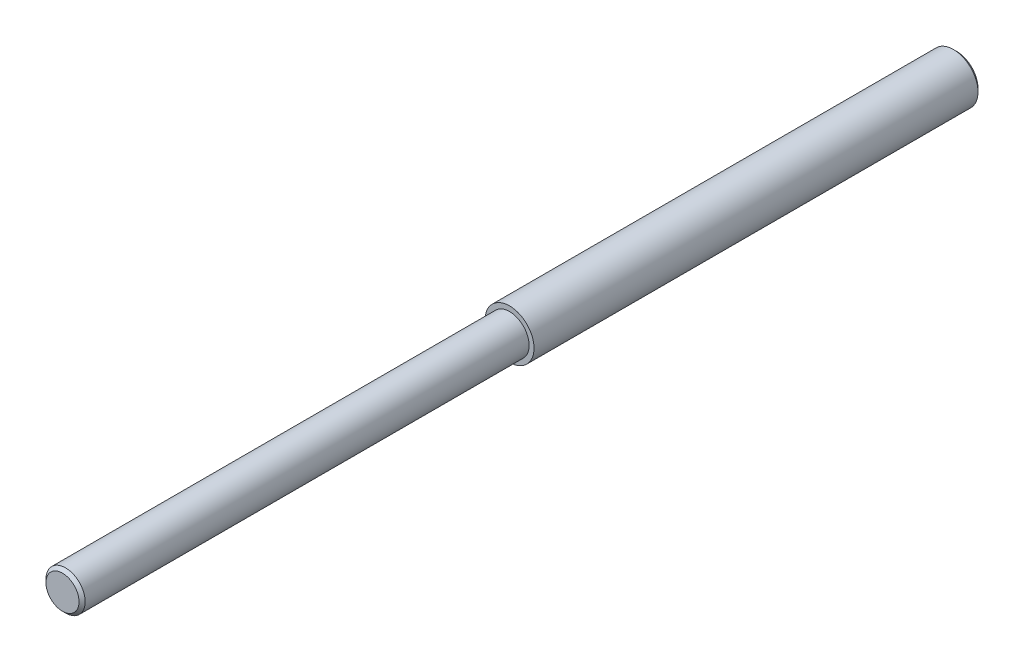
SolidWorks part; units mm, degrees
ref_plane "Front Plane" through (0, 0, 0) normal (0, 0, 1) x (1, 0, 0)
ref_plane "Top Plane" through (0, 0, 0) normal (0, 1, 0) x (1, 0, 0)
ref_plane "Right Plane" through (0, 0, 0) normal (1, 0, 0) x (0, 0, -1)
sketch "Sketch1" plane through (0, 0, 0) normal (0, 0, 1) x (1, 0, 0)
  circle A0 centre (0, 0) radius 4
  dimension "D1" = 8
extrude "Boss-Extrude1" add sketch "Sketch1" along normal blind 73
sketch "Sketch2" plane through (0, 0, 73) normal (0, 0, 1) x (1, 0, 0)
  circle A0 centre (0, 0) radius 3.2
  dimension "D1" = 6.4
extrude "Boss-Extrude2" add sketch "Sketch2" along normal blind 73
ref_axis "Axis2" through (0, 0, 153.3) along (0, 0, -1)
chamfer "Chamfer1" distance 0.5 angle 45 2 edges at (4, 0, 0) (3.2, 0, 146)
